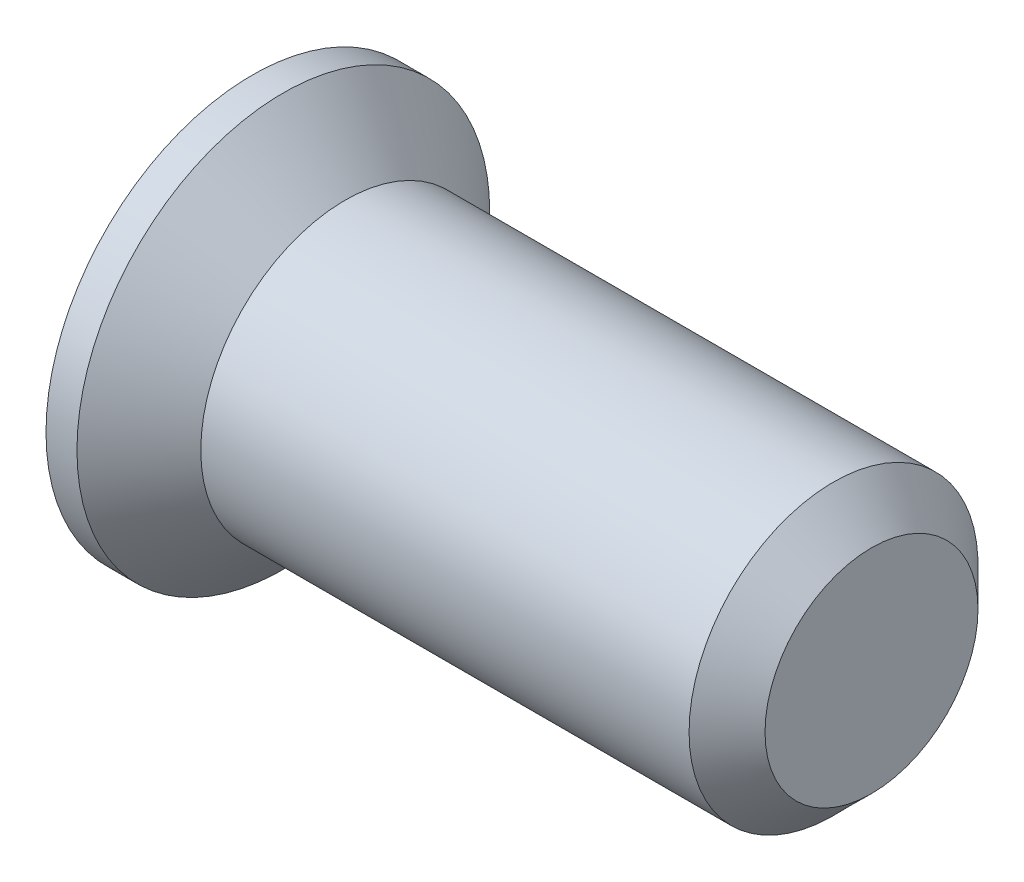
SolidWorks part; units mm, degrees
ref_plane "Front Plane" through (0, 0, 0) normal (0, 0, 1) x (1, 0, 0)
ref_plane "Top Plane" through (0, 0, 0) normal (0, 1, 0) x (1, 0, 0)
ref_plane "Right Plane" through (0, 0, 0) normal (1, 0, 0) x (0, 0, -1)
ref_plane "Plane1" through (0, 0, 0) normal (0, 0, 1) x (1, 0, 0)
sketch "Sketch1" plane through (0, 0, 0) normal (0, 0, 1) x (1, 0, 0)
  line L0 (-0.45, 0) -> (-0.45, 1)
  line L1 (-0.45, 1) -> (-0.3, 1)
  line L2 (-0.3, 1) -> (0, 0.7)
  line L3 (0, 0.7) -> (2.366, 0.7)
  line L4 (2.366, 0.7) -> (2.55, 0.516)
  line L5 (2.55, 0.516) -> (2.55, 0)
  line L6 (2.55, 0) -> (-0.45, 0)
  line L7 (2.55, 0) -> (-0.45, 0) construction
revolve "Revolve1" add sketch "Sketch1" angle 360 about L7 reverse direction yes
cosmetic thread "Cosmetic Thread1" parameters "D1"=2.1, "D2"=1.032
ref_plane "Plane2" through (0, 0, 0) normal (0, 0, 1) x (1, 0, 0)
sketch "Sketch2" plane through (0, 0, 0) normal (0, 0, 1) x (1, 0, 0)
  line L0 (-0.45, -0.6) -> (0.225, -0.3)
  line L1 (0.225, -0.3) -> (0.3375, 0)
  line L2 (0.3375, 0) -> (0.225, 0.3)
  line L3 (0.225, 0.3) -> (-0.45, 0.6)
  line L4 (-0.45, 0.6) -> (-0.45, -0.6)
extrude "Cut-Extrude1" cut sketch "Sketch2" against normal blind 0.1 and the other way blind 0.1
ref_plane "Plane3" through (0, 0, 0) normal (0, 1, 0) x (1, 0, 0)
sketch "Sketch3" plane through (0, 0, 0) normal (0, 1, 0) x (1, 0, 0)
  line L0 (-0.45, -0.6) -> (0.225, -0.3)
  line L1 (0.225, -0.3) -> (0.3375, 0)
  line L2 (0.3375, 0) -> (0.225, 0.3)
  line L3 (0.225, 0.3) -> (-0.45, 0.6)
  line L4 (-0.45, 0.6) -> (-0.45, -0.6)
extrude "Cut-Extrude2" cut sketch "Sketch3" against normal blind 0.1 and the other way blind 0.1
